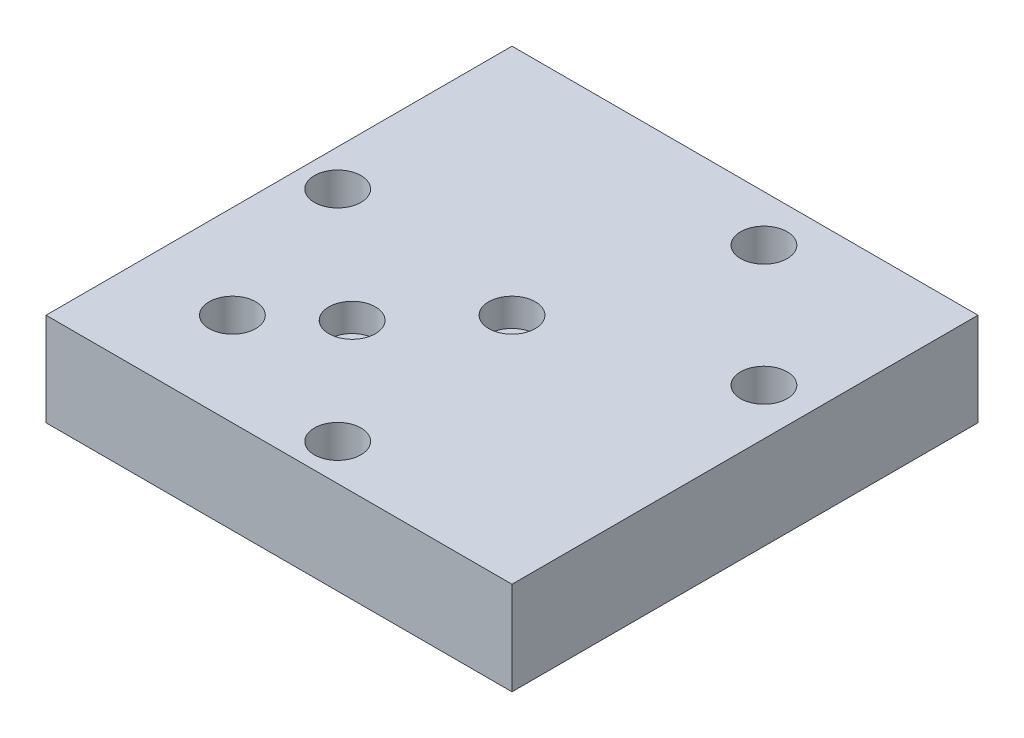
SolidWorks part; units mm, degrees
ref_plane "Front Plane" through (0, 0, 0) normal (0, 0, 1) x (1, 0, 0)
ref_plane "Top Plane" through (0, 0, 0) normal (0, 1, 0) x (1, 0, 0)
ref_plane "Right Plane" through (0, 0, 0) normal (1, 0, 0) x (0, 0, -1)
sketch "Sketch1" plane through (0, 0, 0) normal (0, 1, 0) x (1, 0, 0)
  line L1 (-635, -635) -> (635, -635)
  line L2 (-635, -635) -> (-635, 635)
  line L3 (-635, 635) -> (635, 635)
  line L4 (635, -635) -> (635, 635)
  line L5 (-635, -635) -> (635, 635) construction
  line L6 (-635, 635) -> (635, -635) construction
  circle A0 centre (-381, -381) radius 63.5
  circle A1 centre (-535.4274, 60.3282) radius 63.5
  circle A3 centre (177.9594, 508.5788) radius 63.5
  circle A4 centre (508.5788, 177.9594) radius 63.5
  circle A6 centre (60.3282, -535.4274) radius 63.5
  circle A7 centre (-286.6671, 456.228) radius 63.5 [skipped]
  circle A8 centre (456.228, -286.6671) radius 63.5 [skipped]
  point P0 (0, 0)
  point P22 (0, 0)
  dimension "D3" = 127
  dimension "D1" = 1270
  dimension "D2" = 1270
  dimension "D4" = 254
  dimension "D5" = 254
  dimension "D7" = 99.5726
  dimension "D8" = 695.3282
  dimension "D6" = 7
extrude "Boss-Extrude1" add sketch "Sketch1" along normal blind 254
hole_wizard "CBORE for #00 Binding Head Machine Screw1" positions "Sketch2" profile "Sketch3" counterbore size "#00" standard "ANSI Inch" end condition through all
sketch "Sketch2" plane through (0, 254, 0) normal (0, 1, 0) x (1, 0, 0)
  point P0 (0, 0)
  point P4 (-205.8359, -229.8587)
sketch "Sketch3" plane through (0, 254, 0) normal (1, 0, 0) x (0, 0, 1)
  line L0 (0, 0) -> (0, 254)
  line L1 (0, 254) -> (38.1, 254)
  line L3 (38.1, 254) -> (38.1, 76.2)
  line L4 (38.1, 76.2) -> (63.5, 76.2)
  line L5 (63.5, 76.2) -> (63.5, 0)
  line L7 (63.5, 0) -> (0, 0)
  line L11 (0, -6.35) -> (0, 107.95) construction
  dimension "Thru Hole Dia." = 76.2
  dimension "Thru Hole Depth" = 254
  dimension "C'Bore Dia." = 127
  dimension "C'Bore Depth" = 76.2
